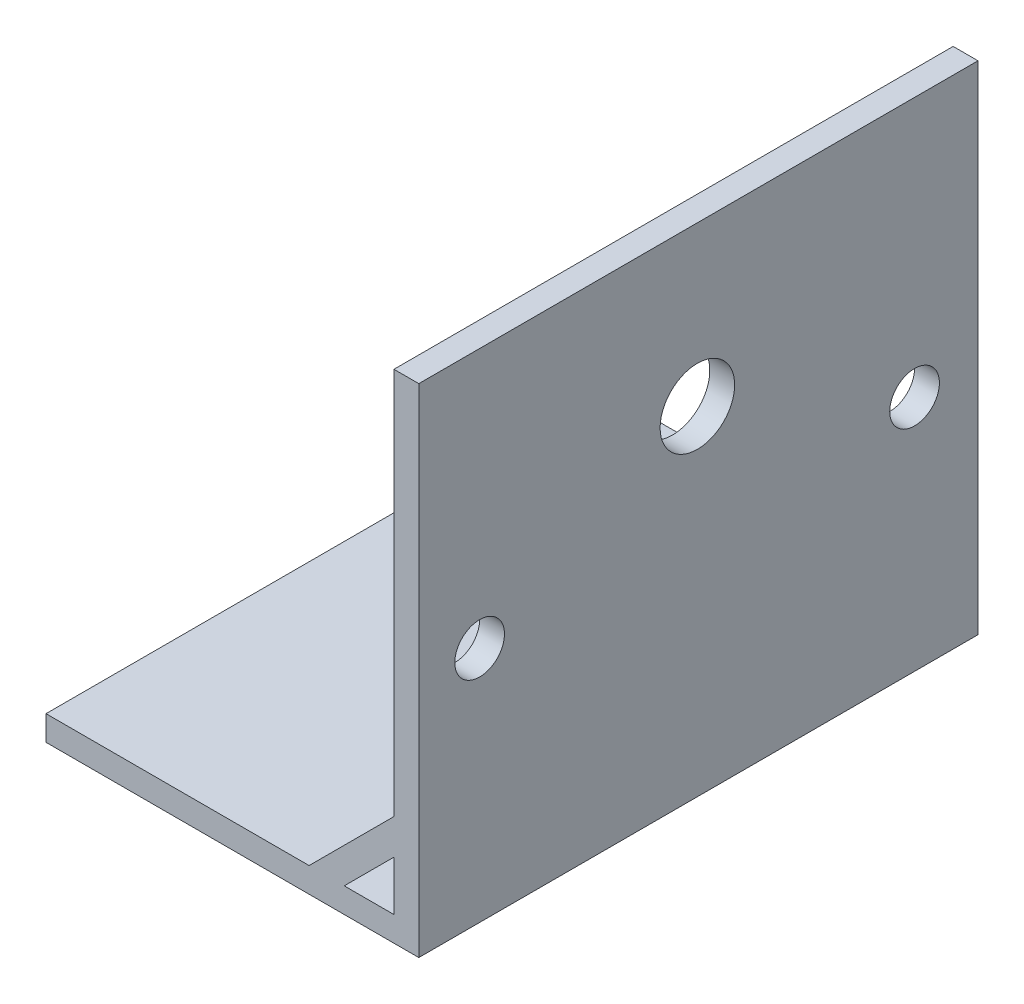
SolidWorks part; units mm, degrees
ref_plane "Front Plane" through (0, 0, 0) normal (0, 0, 1) x (1, 0, 0)
ref_plane "Top Plane" through (0, 0, 0) normal (0, 1, 0) x (1, 0, 0)
ref_plane "Right Plane" through (0, 0, 0) normal (1, 0, 0) x (0, 0, -1)
sketch "Sketch1" plane through (0, 0, 0) normal (0, 1, 0) x (1, 0, 0)
  line L0 (13, -22.5) -> (13, 22.5)
  line L1 (-15, 22.5) -> (15, 22.5)
  line L2 (-15, 22.5) -> (-15, -22.5)
  line L3 (-15, -22.5) -> (15, -22.5)
  line L4 (15, 22.5) -> (15, -22.5)
  line L5 (-15, 22.5) -> (15, -22.5) construction
  line L6 (-15, -22.5) -> (15, 22.5) construction
  point P0 (0, 0)
  dimension "D1" = 30
  dimension "D2" = 45
  dimension "D3" = 2
extrude "Boss-Extrude1" add sketch "Sketch1" along normal blind 2 contours L2 L3 L0 L1 region at (-1, 0, 0)
extrude "Boss-Extrude2" add sketch "Sketch1<3>" along normal blind 40 contours L4 L1 L0 L3 region at (14, 0, 0)
sketch "Sketch1<3>" plane through (0, 0, 0) normal (0, 1, 0) x (1, 0, 0) same geometry as "Sketch1"
sketch "Sketch2" plane through (0, 0, 22.5) normal (0, 0, 1) x (1, 0, 0)
  line L0 (9, 2) -> (13, 6)
  line L1 (-15, 2) -> (13, 2) construction
  line L2 (13, 40) -> (13, 2) construction
  line L3 (7.5858, 3.4142) -> (11.5858, 7.4142) construction
  line L4 (7.5858, 3.4142) -> (6.1716, 2) construction
  line L5 (11.5858, 7.4142) -> (13, 8.8284) construction
  line L6 (6.1716, 2) -> (13, 8.8284)
  line L7 (13, 8.8284) -> (13, 6)
  line L8 (9, 2) -> (6.1716, 2)
  dimension "D1" = 4
  dimension "D2" = 4
  dimension "D3" = 2
extrude "Boss-Extrude3" add sketch "Sketch2" against normal blind 2
ref_plane "Plane1" through (0, 0, 0) normal (0, 0, 1) x (1, 0, 0)
mirror "Mirror1" about plane through (0, 0, 0) normal (0, 0, 1) of "Boss-Extrude3"
sketch "Sketch4" plane through (13, 0, 0) normal (-1, 0, 0) x (0, 0, 1)
  line L0 (0, 40) -> (0, 2) construction
  line L1 (22.5, 40) -> (-22.5, 40) construction
  line L2 (22.5, 2) -> (-22.5, 2) construction
  line L3 (-22.5, 20) -> (22.5, 20) construction
  line L4 (-22.5, 40) -> (-22.5, 8.8284) construction
  line L5 (22.5, 40) -> (22.5, 8.8284) construction
  circle A0 centre (0, 20) radius 3.5555
  circle A1 centre (0.0825, 27.2091) radius 4.5
  circle A2 centre (0.1042, 20.2092) radius 14
  circle A3 centre (-17.3958, 19.1066) radius 2
  circle A4 centre (17.6042, 19.1066) radius 2
  circle A5 centre (0.0825, 27.2091) radius 3
  point P14 (0, 0)
  point P15 (0, 0)
  point P16 (0, 0)
  dimension "D1" = 20
extrude "Cut-Extrude1" cut sketch "Sketch4" against normal through all contours A3 | A4 | A5 region at (13, 19.1066, -17.3958) region at (13, 19.1066, 17.6042) region at (13, 27.2091, 0.0825)
